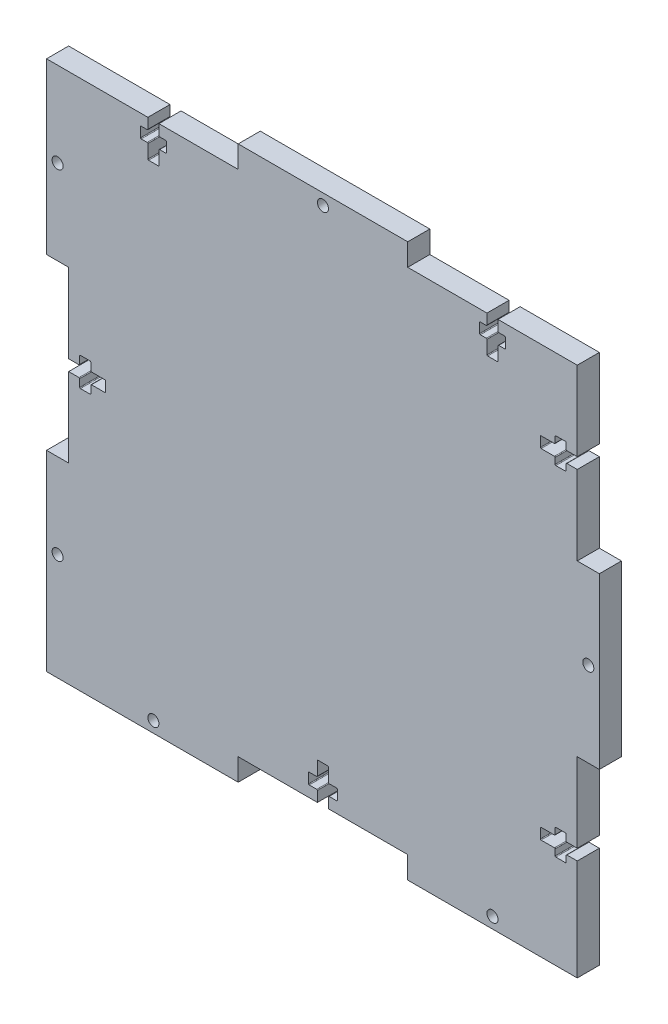
SolidWorks part; units mm, degrees
ref_plane "Front Plane" through (0, 0, 0) normal (0, 0, 1) x (1, 0, 0)
ref_plane "Top Plane" through (0, 0, 0) normal (0, 1, 0) x (1, 0, 0)
ref_plane "Right Plane" through (0, 0, 0) normal (1, 0, 0) x (0, 0, -1)
sketch "Sketch1" plane through (0, 0, 0) normal (0, 0, 1) x (1, 0, 0)
  line L0 (-69, 69) -> (-23, 69)
  line L5 (-75, -75) -> (75, -75) construction
  line L6 (-75, -75) -> (-75, 75) construction
  line L7 (-75, 75) -> (75, 75) construction
  line L8 (75, -75) -> (75, 75) construction
  line L9 (75, 23) -> (69, 23)
  line L10 (69, -23) -> (75, -23)
  line L11 (-69, -69) -> (69, -69) construction
  line L12 (-69, -69) -> (-69, 69) construction
  line L13 (-69, 69) -> (69, 69) construction
  line L14 (69, -69) -> (69, 69) construction
  line L15 (-69, -69) -> (69, 69) construction
  line L16 (69, -69) -> (69, -23)
  line L17 (-23, 69) -> (-23, 75)
  line L18 (-23, 75) -> (23, 75)
  line L19 (23, 75) -> (23, 69)
  line L20 (23, 69) -> (69, 69)
  line L21 (75, -23) -> (75, 23)
  line L22 (69, 23) -> (69, 69)
  line L23 (-75, 23) -> (-69, 23)
  line L24 (-69, 69) -> (-75, 69)
  line L25 (-75, 69) -> (-75, 23)
  line L26 (69, -69) -> (69, -75)
  line L27 (69, -75) -> (23, -75)
  line L28 (23, -75) -> (23, -69)
  line L29 (23, -69) -> (-23, -69)
  line L30 (-23, -69) -> (-23, -75)
  line L31 (-23, -75) -> (-69, -75)
  line L32 (-69, -75) -> (-69, -69) construction
  line L33 (-69, 23) -> (-69, -23)
  line L34 (-69, -23) -> (-75, -23)
  line L35 (-75, -23) -> (-75, -69)
  line L36 (-75, -69) -> (-69, -69) construction
  line L37 (-46, 69) -> (-46, -75) construction
  line L38 (-69, 69) -> (69, -69) construction
  line L39 (-75, -75) -> (-69, -75)
  line L40 (-75, -75) -> (-75, -69)
  point P0 (0, 0)
  point P6 (-7, -7)
  point P26 (0, -75)
  point P27 (-75, 0)
  dimension "D1" = 150
  dimension "D2" = 150
  dimension "D3" = 6
  dimension "D4" = 138
  dimension "D5" = 46
  dimension "D6" = 6
  dimension "D7" = 6
extrude "Box Side" add sketch "Sketch1" along normal blind 6
sketch "Sketch2" plane through (0, 0, 6) normal (0, 0, 1) x (1, 0, 0)
  line L0 (23, 72) -> (-23, 72) construction
  line L1 (23, 75) -> (23, 69) construction
  line L2 (-23, 69) -> (-23, 75) construction
  line L3 (-46, 69) -> (-46, -75) construction
  line L5 (0, 75) -> (0, 69) construction
  line L6 (-23, 75) -> (23, 75) construction
  line L7 (-69, 69) -> (69, 69) construction
  line L16 (-46, 69) -> (-46, -75) construction
  line L21 (0, -69) -> (0, 69) construction
  line L35 (-69, 69) -> (-23, 69) construction
  line L36 (-44.5, 69) -> (-44.5, 66.2)
  line L37 (-44.3, 66) -> (-42.7, 66)
  line L38 (-42.5, 65.8) -> (-42.5, 63.2)
  line L39 (-42.7, 63) -> (-44.3, 63)
  line L40 (-44.5, 62.8) -> (-44.5, 59.2)
  line L46 (-44.7, 59) -> (-47.3, 59)
  line L48 (-44.5, 69) -> (-47.5, 69)
  line L51 (-47.5, 62.8) -> (-47.5, 59.2)
  line L52 (-49.3, 63) -> (-47.7, 63)
  line L53 (-49.5, 65.8) -> (-49.5, 63.2)
  line L54 (-47.7, 66) -> (-49.3, 66)
  line L55 (-47.5, 69) -> (-47.5, 66.2)
  line L56 (47.5, 69) -> (47.5, 66.2)
  line L57 (47.7, 66) -> (49.3, 66)
  line L58 (49.5, 65.8) -> (49.5, 63.2)
  line L59 (49.3, 63) -> (47.7, 63)
  line L60 (47.5, 62.8) -> (47.5, 59.2)
  line L61 (44.5, 69) -> (47.5, 69)
  line L62 (44.7, 59) -> (47.3, 59)
  line L63 (44.5, 62.8) -> (44.5, 59.2)
  line L64 (42.7, 63) -> (44.3, 63)
  line L65 (42.5, 65.8) -> (42.5, 63.2)
  line L66 (44.3, 66) -> (42.7, 66)
  line L67 (44.5, 69) -> (44.5, 66.2)
  line L68 (-69, -69) -> (69, 69) construction
  line L69 (-69, -69) -> (69, 69) construction
  line L70 (75, 0) -> (69, 0) construction
  line L71 (72, 23) -> (72, -23) construction
  line L72 (69, 44.5) -> (66.2, 44.5)
  line L73 (66, 44.3) -> (66, 42.7)
  line L74 (65.8, 42.5) -> (63.2, 42.5)
  line L75 (63, 42.7) -> (63, 44.3)
  line L76 (62.8, 44.5) -> (59.2, 44.5)
  line L77 (59, 44.7) -> (59, 47.3)
  line L78 (69, 44.5) -> (69, 47.5)
  line L79 (62.8, 47.5) -> (59.2, 47.5)
  line L80 (63, 49.3) -> (63, 47.7)
  line L81 (65.8, 49.5) -> (63.2, 49.5)
  line L82 (66, 47.7) -> (66, 49.3)
  line L83 (69, 47.5) -> (66.2, 47.5)
  line L84 (69, -47.5) -> (66.2, -47.5)
  line L85 (66, -47.7) -> (66, -49.3)
  line L86 (65.8, -49.5) -> (63.2, -49.5)
  line L87 (63, -49.3) -> (63, -47.7)
  line L88 (62.8, -47.5) -> (59.2, -47.5)
  line L89 (69, -44.5) -> (69, -47.5)
  line L90 (59, -44.7) -> (59, -47.3)
  line L91 (62.8, -44.5) -> (59.2, -44.5)
  line L92 (63, -42.7) -> (63, -44.3)
  line L93 (65.8, -42.5) -> (63.2, -42.5)
  line L94 (66, -44.3) -> (66, -42.7)
  line L95 (69, -44.5) -> (66.2, -44.5)
  line L120 (-69, 69) -> (69, -69) construction
  line L121 (-69, 69) -> (69, -69) construction
  line L122 (-1.5, -69) -> (1.5, -69)
  line L123 (-23, -69) -> (23, -69) construction
  line L124 (1.5, -69) -> (1.5, -66.2)
  line L125 (1.7, -66) -> (3.7, -66)
  line L126 (3.9, -65.8) -> (3.9, -63.2)
  line L127 (3.7, -63) -> (1.7, -63)
  line L128 (1.5, -62.8) -> (1.5, -59.2)
  line L129 (1.3, -59) -> (-1.3, -59)
  line L130 (-1.5, -62.8) -> (-1.5, -59.2)
  line L131 (-3.7, -63) -> (-1.7, -63)
  line L132 (-3.9, -65.8) -> (-3.9, -63.2)
  line L133 (-1.7, -66) -> (-3.7, -66)
  line L134 (-1.5, -69) -> (-1.5, -66.2)
  line L135 (-69, -1.5) -> (-66.2, -1.5)
  line L136 (-66, -1.7) -> (-66, -3.7)
  line L137 (-65.8, -3.9) -> (-63.2, -3.9)
  line L138 (-63, -3.7) -> (-63, -1.7)
  line L139 (-62.8, -1.5) -> (-59.2, -1.5)
  line L140 (-59, 1.3) -> (-59, -1.3)
  line L141 (-62.8, 1.5) -> (-59.2, 1.5)
  line L142 (-63, 3.7) -> (-63, 1.7)
  line L143 (-65.8, 3.9) -> (-63.2, 3.9)
  line L144 (-66, 1.7) -> (-66, 3.7)
  line L145 (-69, 1.5) -> (-66.2, 1.5)
  line L146 (-69, -1.5) -> (-69, 1.5)
  line L147 (-69, -72) -> (-23, -72) construction
  line L149 (-23, -75) -> (-23, -69) construction
  line L150 (-69, -69) -> (-69, -75) construction
  line L151 (-75, -75) -> (-23, -75) construction
  circle A0 centre (0, 72) radius 1.5
  arc A1 (-44.5, 59.2) -> (-44.7, 59) centre (-44.7, 59.2) cw
  arc A2 (-44.3, 63) -> (-44.5, 62.8) centre (-44.3, 62.8) ccw
  arc A3 (-42.5, 63.2) -> (-42.7, 63) centre (-42.7, 63.2) cw
  arc A4 (-42.7, 66) -> (-42.5, 65.8) centre (-42.7, 65.8) cw
  arc A5 (-44.5, 66.2) -> (-44.3, 66) centre (-44.3, 66.2) ccw
  arc A6 (-47.5, 66.2) -> (-47.7, 66) centre (-47.7, 66.2) cw
  arc A7 (-49.3, 66) -> (-49.5, 65.8) centre (-49.3, 65.8) ccw
  arc A8 (-49.5, 63.2) -> (-49.3, 63) centre (-49.3, 63.2) ccw
  arc A9 (-47.7, 63) -> (-47.5, 62.8) centre (-47.7, 62.8) cw
  arc A10 (-47.5, 59.2) -> (-47.3, 59) centre (-47.3, 59.2) ccw
  arc A11 (47.5, 59.2) -> (47.3, 59) centre (47.3, 59.2) cw
  arc A12 (47.7, 63) -> (47.5, 62.8) centre (47.7, 62.8) ccw
  arc A13 (49.5, 63.2) -> (49.3, 63) centre (49.3, 63.2) cw
  arc A14 (49.3, 66) -> (49.5, 65.8) centre (49.3, 65.8) cw
  arc A15 (47.5, 66.2) -> (47.7, 66) centre (47.7, 66.2) ccw
  arc A16 (44.5, 66.2) -> (44.3, 66) centre (44.3, 66.2) cw
  arc A17 (42.7, 66) -> (42.5, 65.8) centre (42.7, 65.8) ccw
  arc A18 (42.5, 63.2) -> (42.7, 63) centre (42.7, 63.2) ccw
  arc A19 (44.3, 63) -> (44.5, 62.8) centre (44.3, 62.8) cw
  arc A20 (44.5, 59.2) -> (44.7, 59) centre (44.7, 59.2) ccw
  arc A21 (59.2, 44.5) -> (59, 44.7) centre (59.2, 44.7) cw
  arc A22 (63, 44.3) -> (62.8, 44.5) centre (62.8, 44.3) ccw
  arc A23 (63.2, 42.5) -> (63, 42.7) centre (63.2, 42.7) cw
  arc A24 (66, 42.7) -> (65.8, 42.5) centre (65.8, 42.7) cw
  arc A25 (66.2, 44.5) -> (66, 44.3) centre (66.2, 44.3) ccw
  arc A26 (66.2, 47.5) -> (66, 47.7) centre (66.2, 47.7) cw
  arc A27 (66, 49.3) -> (65.8, 49.5) centre (65.8, 49.3) ccw
  arc A28 (63.2, 49.5) -> (63, 49.3) centre (63.2, 49.3) ccw
  arc A29 (63, 47.7) -> (62.8, 47.5) centre (62.8, 47.7) cw
  arc A30 (59.2, 47.5) -> (59, 47.3) centre (59.2, 47.3) ccw
  arc A31 (59.2, -47.5) -> (59, -47.3) centre (59.2, -47.3) cw
  arc A32 (63, -47.7) -> (62.8, -47.5) centre (62.8, -47.7) ccw
  arc A33 (63.2, -49.5) -> (63, -49.3) centre (63.2, -49.3) cw
  arc A34 (66, -49.3) -> (65.8, -49.5) centre (65.8, -49.3) cw
  arc A35 (66.2, -47.5) -> (66, -47.7) centre (66.2, -47.7) ccw
  arc A36 (66.2, -44.5) -> (66, -44.3) centre (66.2, -44.3) cw
  arc A37 (66, -42.7) -> (65.8, -42.5) centre (65.8, -42.7) ccw
  arc A38 (63.2, -42.5) -> (63, -42.7) centre (63.2, -42.7) ccw
  arc A39 (63, -44.3) -> (62.8, -44.5) centre (62.8, -44.3) cw
  arc A40 (59.2, -44.5) -> (59, -44.7) centre (59.2, -44.7) ccw
  circle A41 centre (72, 0) radius 1.5
  arc A62 (1.5, -59.2) -> (1.3, -59) centre (1.3, -59.2) ccw
  arc A63 (1.7, -63) -> (1.5, -62.8) centre (1.7, -62.8) cw
  arc A64 (3.9, -63.2) -> (3.7, -63) centre (3.7, -63.2) ccw
  arc A65 (3.7, -66) -> (3.9, -65.8) centre (3.7, -65.8) ccw
  arc A66 (1.5, -66.2) -> (1.7, -66) centre (1.7, -66.2) cw
  arc A67 (-1.5, -66.2) -> (-1.7, -66) centre (-1.7, -66.2) ccw
  arc A68 (-3.7, -66) -> (-3.9, -65.8) centre (-3.7, -65.8) cw
  arc A69 (-3.9, -63.2) -> (-3.7, -63) centre (-3.7, -63.2) cw
  arc A70 (-1.7, -63) -> (-1.5, -62.8) centre (-1.7, -62.8) ccw
  arc A71 (-1.5, -59.2) -> (-1.3, -59) centre (-1.3, -59.2) cw
  arc A72 (-59.2, -1.5) -> (-59, -1.3) centre (-59.2, -1.3) ccw
  arc A73 (-63, -1.7) -> (-62.8, -1.5) centre (-62.8, -1.7) cw
  arc A74 (-63.2, -3.9) -> (-63, -3.7) centre (-63.2, -3.7) ccw
  arc A75 (-66, -3.7) -> (-65.8, -3.9) centre (-65.8, -3.7) ccw
  arc A76 (-66.2, -1.5) -> (-66, -1.7) centre (-66.2, -1.7) cw
  arc A77 (-66.2, 1.5) -> (-66, 1.7) centre (-66.2, 1.7) ccw
  arc A78 (-66, 3.7) -> (-65.8, 3.9) centre (-65.8, 3.7) cw
  arc A79 (-63.2, 3.9) -> (-63, 3.7) centre (-63.2, 3.7) cw
  arc A80 (-63, 1.7) -> (-62.8, 1.5) centre (-62.8, 1.7) ccw
  arc A81 (-59.2, 1.5) -> (-59, 1.3) centre (-59.2, 1.3) cw
  circle A82 centre (-46, -72) radius 1.5
  circle A83 centre (46, -72) radius 1.5
  circle A84 centre (-72, 46) radius 1.5
  circle A85 centre (-72, -46) radius 1.5
  point P6 (0, 72)
  point P38 (0, 0)
  point P56 (-46, 59)
  point P88 (46, 59)
  point P161 (59, 46)
  point P162 (59, -46)
  point P198 (0, -59)
  point P231 (-59, 0)
  point P234 (0, 0)
  point P246 (0, 0)
  dimension "D1" = 3
  dimension "D2" = 0.2
  dimension "D8" = 0.2
  dimension "D14" = 3
  dimension "D3" = 3
  dimension "D4" = 3
  dimension "D5" = 4
  dimension "D6" = 2
  dimension "D7" = 1.5
  dimension "D9" = 3
  dimension "D10" = 3
  dimension "D11" = 4
  dimension "D12" = 1.5
  dimension "D13" = 2
extrude "Screw Cut-outs" cut sketch "Sketch2" against normal through all
